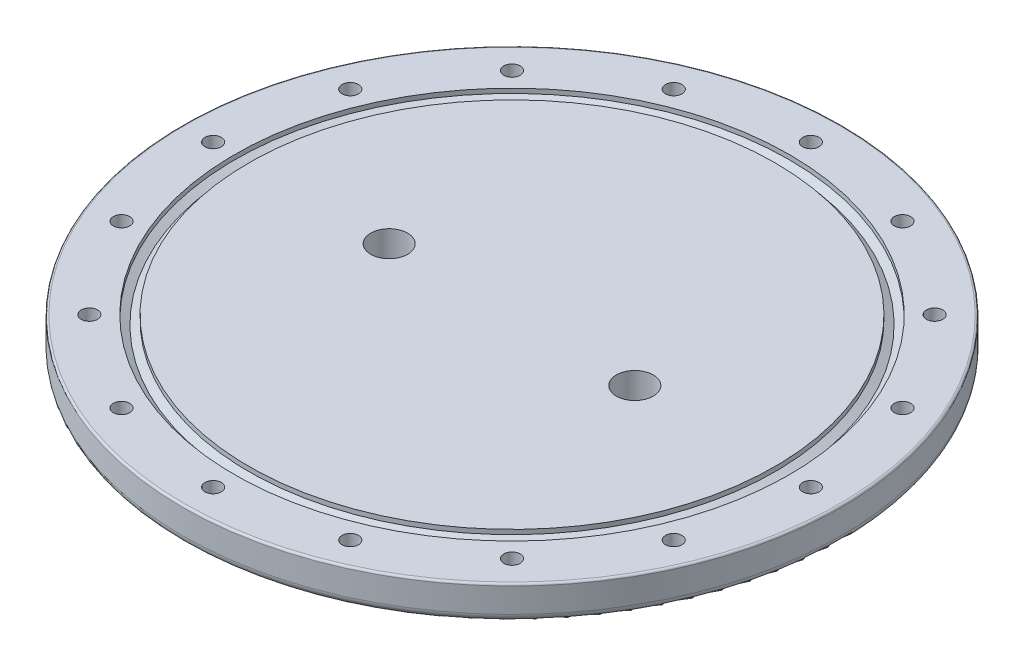
SolidWorks part; units mm, degrees
ref_plane "Front Plane" through (0, 0, 0) normal (0, 0, 1) x (1, 0, 0)
ref_plane "Top Plane" through (0, 0, 0) normal (0, 1, 0) x (1, 0, 0)
ref_plane "Right Plane" through (0, 0, 0) normal (1, 0, 0) x (0, 0, -1)
sketch "Sketch1" plane through (0, 0, 0) normal (0, 1, 0) x (1, 0, 0)
  circle A0 centre (0, 0) radius 80.5
  dimension "D1" = 161
extrude "Boss-Extrude1" add sketch "Sketch1" along normal blind 8.5 contours A0
sketch "Sketch2" plane through (0, 8.5, 0) normal (0, 1, 0) x (1, 0, 0)
  circle A0 centre (0, 0) radius 73 construction
  circle A1 centre (0, 73) radius 2
  circle A2 centre (27.9359, 67.4432) radius 2
  circle A3 centre (51.6188, 51.6188) radius 2
  circle A4 centre (67.4432, 27.9359) radius 2
  circle A5 centre (73, 0) radius 2
  circle A6 centre (67.4432, -27.9359) radius 2
  circle A7 centre (51.6188, -51.6188) radius 2
  circle A8 centre (27.9359, -67.4432) radius 2
  circle A9 centre (0, -73) radius 2
  circle A10 centre (-27.9359, -67.4432) radius 2
  circle A11 centre (-51.6188, -51.6188) radius 2
  circle A12 centre (-67.4432, -27.9359) radius 2
  circle A13 centre (-73, 0) radius 2
  circle A14 centre (-67.4432, 27.9359) radius 2
  circle A15 centre (-51.6188, 51.6188) radius 2
  circle A16 centre (-27.9359, 67.4432) radius 2
  point P38 (0, 0)
  dimension "D1" = 146
  dimension "D2" = 4
  dimension "D3" = 16
extrude "Cut-Extrude1" cut sketch "Sketch2" against normal up to next
sketch "Sketch5" plane through (0, 0, 0) normal (0, -1, 0) x (1, 0, 0)
  circle A0 centre (30, 0) radius 4.5
  circle A1 centre (-30, 0) radius 4.5
  circle A2 centre (0, 0) radius 30 construction
  dimension "D1" = 9
  dimension "D3" = 60
extrude "Cut-Extrude2" cut sketch "Sketch5" against normal up to next
sketch "Sketch4" plane through (0, 0, 0) normal (0, 0, 1) x (1, 0, 0)
  line L0 (0, 0) -> (66, 0) construction
  line L1 (-80.5, 0) -> (80.5, 0) construction
  line L2 (66, 0) -> (66, 8.5) construction
  line L3 (69.4432, 8.5) -> (65.4432, 8.5) construction
  line L5 (67.75, 7.3804) -> (67.75, 8.5)
  line L6 (67.75, 8.5) -> (64.25, 8.5)
  line L7 (64.25, 8.5) -> (64.25, 7.3804)
  line L9 (0, 0) -> (0, 12.8224) construction
  line L10 (64.25, 7.3804) -> (66, 6.37)
  line L11 (66, 6.37) -> (67.75, 7.3804)
  line L12 (66, 6.37) -> (62.9643, 6.37) construction
  dimension "D1" = 66
  dimension "D2" = 3.5
  dimension "D3" = 2.13
  dimension "D4" = 30
revolve "Cut-Revolve1" cut sketch "Sketch4" angle 360 about L9
fillet "Fillet1" radius 2 1 edges at (0, 0, 80.5)
fillet "Fillet2" radius 0.5 1 edges at (0, 8.5, 80.5)
